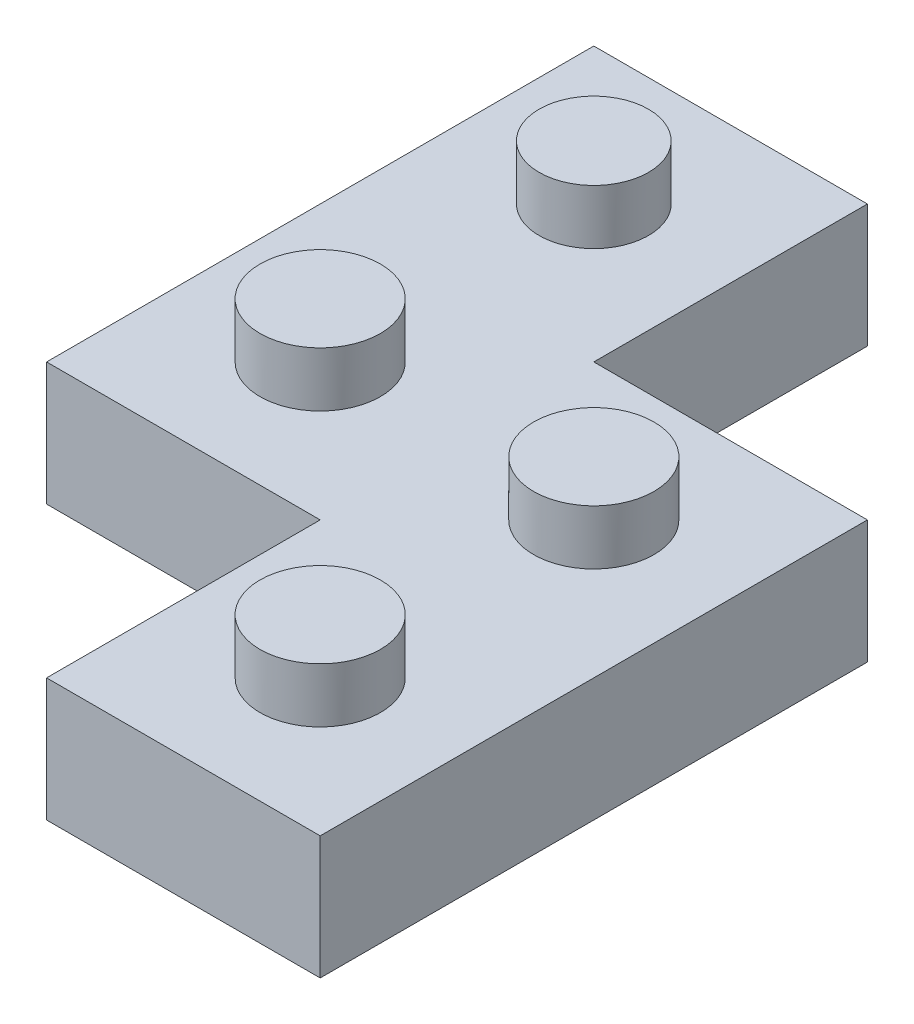
SolidWorks part; units mm, degrees
material "ABS"
ref_plane "Front Plane" through (0, 0, 0) normal (0, 0, 1) x (1, 0, 0)
ref_plane "Top Plane" through (0, 0, 0) normal (0, 1, 0) x (1, 0, 0)
ref_plane "Right Plane" through (0, 0, 0) normal (1, 0, 0) x (0, 0, -1)
sketch "Sketch1" plane through (0, 0, 0) normal (0, 1, 0) x (1, 0, 0)
  line L0 (-5.6746, 20.3112) -> (7.0254, 20.3112)
  line L1 (7.0254, 20.3112) -> (7.0254, 7.6112)
  line L2 (7.0254, 7.6112) -> (19.7254, 7.6112)
  line L3 (19.7254, 7.6112) -> (19.7254, -17.7888)
  line L4 (19.7254, -17.7888) -> (7.0254, -17.7888)
  line L5 (7.0254, -17.7888) -> (7.0254, -5.0888)
  line L6 (7.0254, -5.0888) -> (-5.6746, -5.0888)
  line L7 (-5.6746, -5.0888) -> (-5.6746, 20.3112)
  dimension "D1" = 38.1
  dimension "D2" = 12.7
  dimension "D3" = 12.7
  dimension "D4" = 12.7
  dimension "D5" = 12.7
extrude "Boss-Extrude1" add sketch "Sketch1" along normal blind 5.715
sketch "Sketch2" plane through (0, 5.715, 0) normal (0, 1, 0) x (1, 0, 0)
  line L0 (-5.6746, 20.3112) -> (-5.6746, -5.0888) construction
  line L1 (19.7254, -17.7888) -> (19.7254, 7.6112) construction
  line L2 (7.0254, 20.3112) -> (-5.6746, 20.3112) construction
  circle A0 centre (0.6754, 1.2612) radius 2.794
  circle A1 centre (13.3754, 1.2612) radius 2.794
  circle A2 centre (0.6754, 13.9612) radius 2.54
  circle A3 centre (13.3754, -11.4388) radius 2.794
  dimension "D2" = 6.35
  dimension "D4" = 6.35
  dimension "D5" = 12.7
  dimension "D3" = 6.35
  dimension "D6" = 12.7
  dimension "D1" = 2
extrude "Boss-Extrude3" add sketch "Sketch2" along normal blind 2.54
